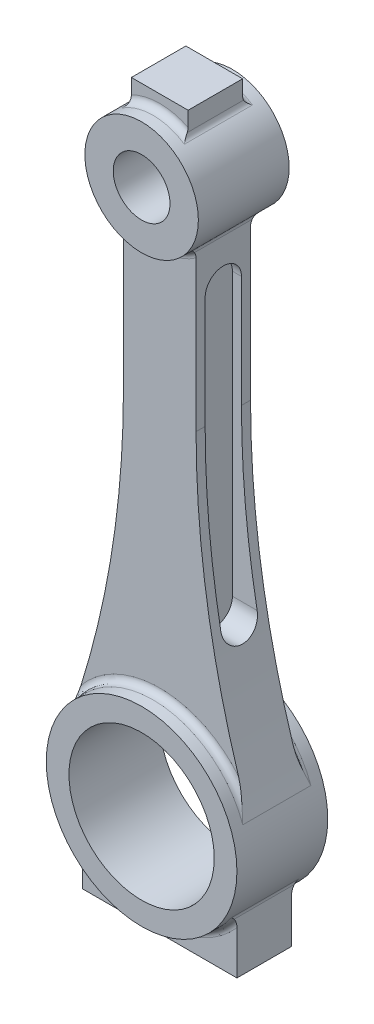
SolidWorks part; units mm, degrees
ref_plane "Front Plane" through (0, 0, 0) normal (0, 0, 1) x (1, 0, 0)
ref_plane "Top Plane" through (0, 0, 0) normal (0, 1, 0) x (1, 0, 0)
ref_plane "Right Plane" through (0, 0, 0) normal (1, 0, 0) x (0, 0, -1)
sketch "Sketch1" plane through (0, 0, 0) normal (0, 0, 1) x (1, 0, 0)
  circle A1 centre (0, 0) radius 16
  circle A2 centre (0, 0) radius 21
  circle A3 centre (0, 120) radius 12.5
  circle A4 centre (0, 120) radius 6.25
  point P1 (0, 0)
  point P8 (0, 0)
  point P9 (0, 0)
  point P10 (0, 0)
  dimension "D1" = 42
  dimension "D2" = 32
  dimension "D3" = 25
  dimension "D4" = 12.5
  dimension "D5" = 120
extrude "Boss-Extrude1" add sketch "Sketch1" along normal mid plane 20
sketch "Sketch2" plane through (0, 0, 0) normal (0, 0, 1) x (1, 0, 0)
  line L0 (8, 110.3953) -> (8, 75.3953)
  line L1 (0, 120) -> (0, 89.0112) construction
  line L2 (-8, 110.3953) -> (-8, 75.3953)
  arc A0 (8, 75.3953) -> (19.7874, 7.0327) centre (212.1328, 75.3953) ccw
  circle A1 centre (0, 0) radius 21 construction
  arc A2 (-8, 75.3953) -> (-19.7874, 7.0327) centre (-212.1328, 75.3953) cw
  circle A3 centre (0, 120) radius 12.5 construction
  arc A4 (-8, 110.3953) -> (8, 110.3953) centre (0, 120) ccw
  arc A5 (19.7874, 7.0327) -> (-19.7874, 7.0327) centre (0, 0) ccw
  dimension "D1" = 8
  dimension "D2" = 35
  dimension "D3" = 35
extrude "Boss-Extrude2" add sketch "Sketch2" along normal mid plane 12
sketch "Sketch3" plane through (0, 0, 0) normal (0, 0, 1) x (1, 0, 0)
  line L0 (0, 192.6555) -> (0, -57.9582) construction
  line L1 (-6.25, 130.8253) -> (-6.25, 135.8253)
  line L2 (6.25, 130.8253) -> (6.25, 135.8253)
  line L3 (-6.25, 135.8253) -> (6.25, 135.8253)
  line L4 (-17, -12.3288) -> (-17, -24.3288)
  line L5 (17, -12.3288) -> (17, -24.3288)
  line L6 (-17, -24.3288) -> (17, -24.3288)
  circle A0 centre (0, 120) radius 12.5 construction
  arc A1 (6.25, 130.8253) -> (-6.25, 130.8253) centre (0, 120) ccw
  circle A2 centre (0, 0) radius 21 construction
  arc A3 (-17, -12.3288) -> (17, -12.3288) centre (0, 0) ccw
  dimension "D1" = 5
  dimension "D2" = 12.5
  dimension "D3" = 12
  dimension "D4" = 34
extrude "Boss-Extrude3" add sketch "Sketch3" along normal mid plane 12
fillet "Fillet1" radius 1.5 4 edges at (6.25, 130.8253, 0) (0, 132.5, -6) (0, 132.5, 6) (-6.25, 130.8253, 0)
fillet "Fillet2" radius 1.5 10 edges at (-17, -12.3288, 0) (0, -21, 6) (17, -12.3288, 0) (0, -21, -6) (0, 21, 6) (0, 21, -6) (0, 107.5, -6) (8, 110.3953, 0) (0, 107.5, 6) (-8, 110.3953, 0)
ref_plane "Plane1" through (6, 0, 0) normal (-1, 0, 0) x (0, 0, 1)
sketch "Sketch4" plane through (6, 0, 0) normal (-1, 0, 0) x (0, 0, 1)
  line L0 (0, 100) -> (0, 38) construction
  line L1 (4, 100) -> (4, 38)
  line L2 (-4, 100) -> (-4, 38)
  line L3 (-10, 120) -> (10, 120) construction
  line L4 (-10, 132.5) -> (-10, 107.5) construction
  line L5 (10, 107.5) -> (10, 132.5) construction
  arc A0 (4, 100) -> (-4, 100) centre (0, 100) ccw
  arc A1 (-4, 38) -> (4, 38) centre (0, 38) ccw
  point P3 (0, 69)
  dimension "D1" = 4
  dimension "D2" = 62
  dimension "D3" = 20
extrude "Cut-Extrude3" cut sketch "Sketch4" against normal through all
mirror "Mirror1" about plane through (0, 0, 0) normal (1, 0, 0) of "Cut-Extrude3"
